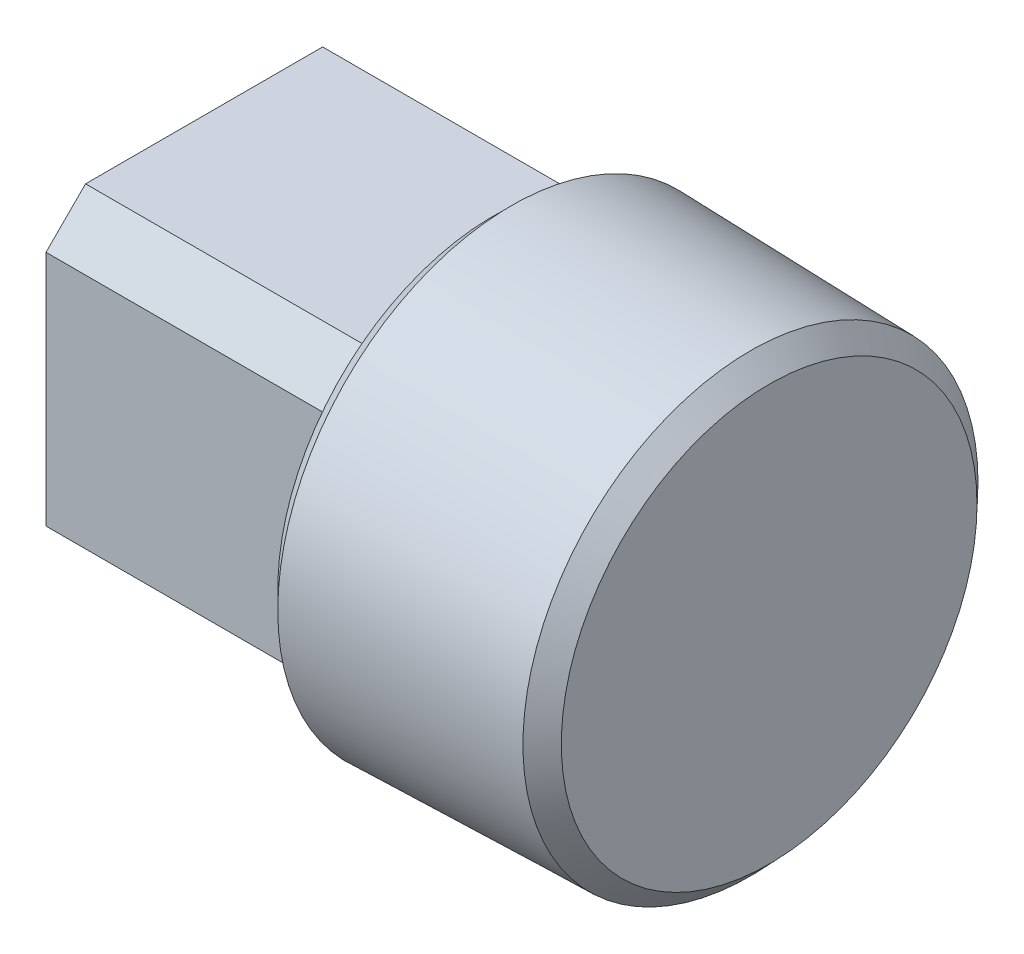
SolidWorks part; units mm, degrees
ref_plane "Front Plane" through (0, 0, 0) normal (0, 0, 1) x (1, 0, 0)
ref_plane "Top Plane" through (0, 0, 0) normal (0, 1, 0) x (1, 0, 0)
ref_plane "Right Plane" through (0, 0, 0) normal (1, 0, 0) x (0, 0, -1)
sketch "Sketch1" plane through (0, 0, 0) normal (0, 0, 1) x (1, 0, 0)
  line L0 (-10.668, 0) -> (10.668, 0) construction
  line L1 (-10.668, 5.969) -> (-10.668, -5.969) construction
  line L2 (10.668, 8.5725) -> (10.668, -8.5725) construction
  line L3 (10.668, -8.5725) -> (5.0255, -8.7203) construction
  point P7 (0.254, 0)
  point P8 (5.0255, -8.7203)
  dimension "D1" = 1.5
  dimension "D2" = 5.6444
ref_plane "Plane1" through (10.668, 0, 0) normal (1, 0, 0) x (0, 0, -1)
sketch "Sketch2" plane through (10.668, 0, 0) normal (1, 0, 0) x (0, 0, -1)
  circle A0 centre (0, 0) radius 8.5725
extrude "Extrude1" add sketch "Sketch2" against normal up to vertex (10.414 mm away) draft 1.5 up to point (0.254, 0, 0) draft outward yes
sketch "Sketch4" plane through (10.668, 0, 0) normal (1, 0, 0) x (0, 0, -1)
  circle A1 centre (0, 0) radius 8.5725
  circle A2 centre (0, 0) radius 8.5725
  dimension "D1" = 0
curve "Helix/Spiral1" parameters "Pitch"=1.4111
sketch "Sketch5" plane through (0, 0, 0) normal (0, 0, 1) x (1, 0, 0)
  line L0 (10.0506, 8.5725) -> (10.5798, 7.656)
  line L1 (10.5798, 7.656) -> (10.7562, 7.656)
  line L2 (10.7562, 7.656) -> (11.2854, 8.5725)
  line L3 (11.2854, 8.5725) -> (9.9107, 8.8149)
  line L4 (11.2854, 8.5725) -> (10.0506, 8.5725) construction
  line L5 (10.0506, 8.5725) -> (9.9107, 8.8149)
  line L6 (10.668, 7.656) -> (10.668, 8.5725) construction
  line L7 (11.0208, 8.1142) -> (10.3152, 8.1142) construction
  dimension "D1" = 10
  dimension "D2" = 0.1764
  dimension "D3" = 0.7056
  dimension "D4" = 60
chamfer "Chamfer1" distance 0.7056 angle 45 2 edges at (10.668, 0, -8.5725) (0.254, 0, -8.8452) first distance on face at (0.254, 0, -8.8452)
sweep "Cut-Sweep1" [suppressed] cut profiles "Sketch5" path "Helix/Spiral1"
sketch "Sketch6" plane through (0.254, 0, 0) normal (-1, 0, 0) x (0, 0, 1)
  line L0 (-5.969, -5.969) -> (5.969, 5.969) construction
  line L1 (-5.969, -5.969) -> (5.969, -5.969)
  line L2 (-5.969, -5.969) -> (-5.969, 5.969)
  line L3 (-5.969, 5.969) -> (5.969, 5.969)
  line L4 (5.969, -5.969) -> (5.969, 5.969)
extrude "Extrude2" add sketch "Sketch6" along normal up to vertex (10.922 mm away) up to point (-10.668, 0, 0)
sketch "Sketch7" plane through (-10.668, 0, 0) normal (-1, 0, 0) x (0, 0, 1)
  line L0 (4.4767, 5.969) -> (5.969, 4.4768)
  line L1 (5.969, -4.4768) -> (4.4767, -5.969)
  line L2 (-5.969, -4.4768) -> (-4.4767, -5.969)
  line L3 (-5.969, 4.4768) -> (-4.4767, 5.969)
  line L4 (-5.969, 5.969) -> (-5.969, -5.969)
  line L5 (-5.969, -5.969) -> (5.969, -5.969)
  line L6 (5.969, -5.969) -> (5.969, 5.969)
  line L7 (5.969, 5.969) -> (-5.969, 5.969)
  line L8 (-5.969, 5.969) -> (-5.969, 4.4768)
  line L9 (-5.969, -5.969) -> (-4.4767, -5.969)
  line L10 (5.969, -5.969) -> (5.969, -4.4768)
  line L11 (5.969, 5.969) -> (4.4767, 5.969)
  line L12 (5.969, 4.4768) -> (5.969, 5.969)
  line L13 (-4.4767, 5.969) -> (-5.969, 5.969)
  line L14 (-5.969, -4.4768) -> (-5.969, -5.969)
  line L15 (4.4767, -5.969) -> (5.969, -5.969)
  dimension "D2" = 1.4922
extrude "Cut-Extrude1" cut sketch "Sketch7" against normal up to vertex (10.922 mm away) up to point (0.254, 0, 0)
equation "\"D2@Sketch5\" = \"Pitch@Helix/Spiral1\"*.125"
equation "\"D3@Sketch5\" = \"Pitch@Helix/Spiral1\"*.5"
equation "\"D1@Chamfer1\" = \"Pitch@Helix/Spiral1\"*.5"
equation "\"D3@Helix/Spiral1\" = \"A@Sketch1\""
equation "\"D2@Sketch7\" = \"B@Sketch1\"/8"
equation "\"D2@Sketch1\" = \"Pitch@Helix/Spiral1\"*4"
